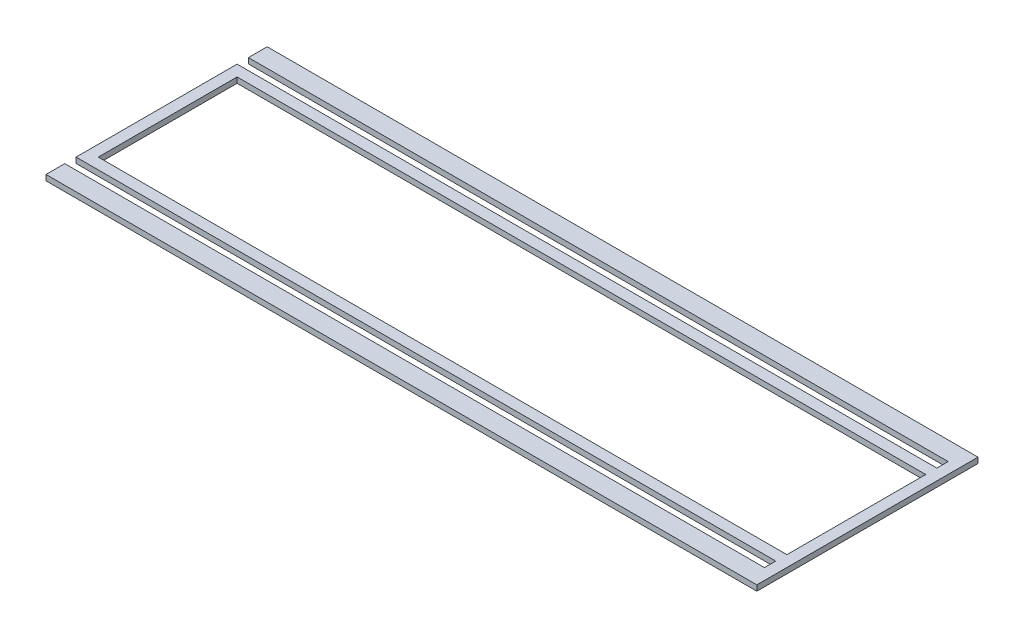
SolidWorks part; units mm, degrees
ref_plane "Front Plane" through (0, 0, 0) normal (0, 0, 1) x (1, 0, 0)
ref_plane "Top Plane" through (0, 0, 0) normal (0, 1, 0) x (1, 0, 0)
ref_plane "Right Plane" through (0, 0, 0) normal (1, 0, 0) x (0, 0, -1)
sketch "Sketch1" plane through (0, 0, 0) normal (0, 1, 0) x (1, 0, 0)
  line L0 (-203.2, 46.0343) -> (-203.2, -46.0343)
  line L1 (-203.2, 63.227) -> (203.2, 63.227)
  line L2 (-203.2, 63.227) -> (-203.2, 52.5113)
  line L3 (-203.2, -63.2269) -> (203.2, -63.2269)
  line L4 (203.2, 63.227) -> (203.2, -63.2269)
  line L5 (-203.2, 63.227) -> (203.2, -63.2269) construction
  line L6 (-203.2, -63.2269) -> (203.2, 63.227) construction
  line L7 (-203.2, -63.2269) -> (190.5, -63.2269)
  line L8 (-203.2, -63.2269) -> (-203.2, -52.5113)
  line L9 (-203.2, -52.5113) -> (196.85, -52.5113)
  line L11 (-203.2, 63.227) -> (190.5, 63.227)
  line L12 (-203.2, 63.227) -> (-203.2, 52.5113)
  line L13 (-203.2, 52.5113) -> (196.85, 52.5113)
  line L15 (-203.2, -52.5113) -> (196.85, -52.5113)
  line L17 (-203.2, -46.0343) -> (196.85, -46.0343)
  line L18 (196.85, -52.5113) -> (196.85, -46.0343)
  line L19 (-203.2, 52.5113) -> (196.85, 52.5113)
  line L21 (-203.2, 46.0343) -> (196.85, 46.0343)
  line L22 (196.85, 52.5113) -> (196.85, 46.0343)
  line L23 (-203.2, -52.5113) -> (-203.2, -63.2269)
  line L25 (-196.85, -39.6843) -> (196.85, -39.6843)
  line L26 (-196.85, -39.6843) -> (-196.85, 39.6843)
  line L27 (-196.85, 39.6843) -> (196.85, 39.6843)
  line L28 (196.85, -39.6843) -> (196.85, 39.6843)
  line L29 (-196.85, -39.6843) -> (196.85, 39.6843) construction
  line L30 (-196.85, 39.6843) -> (196.85, -39.6843) construction
  point P0 (0, 0)
  point P16 (0, 0)
  dimension "D1" = 406.4
  dimension "D2" = 126.4539
  dimension "D4" = 10.7156
  dimension "D5" = 10.7156
  dimension "D6" = 6.477
  dimension "D7" = 6.477
  dimension "D3" = 6.35
  dimension "D8" = 6.35
  dimension "D9" = 6.35
  dimension "D10" = 6.35
extrude "Boss-Extrude1" add sketch "Sketch1" along normal mid plane 3.175 contours L1 L13 L2 L9 L3 L4 region at (-3.175, 0, -41.7781)
equation "\"D2@Sketch1\"     = 5.698in - ( 2 * ( 2 * 0.125in))- 4*3/64-(0.008*4)"
equation "\"D1@Sketch1\"=16.00in"
equation "\"D6@Sketch1\"=\"D7@Sketch1\""
